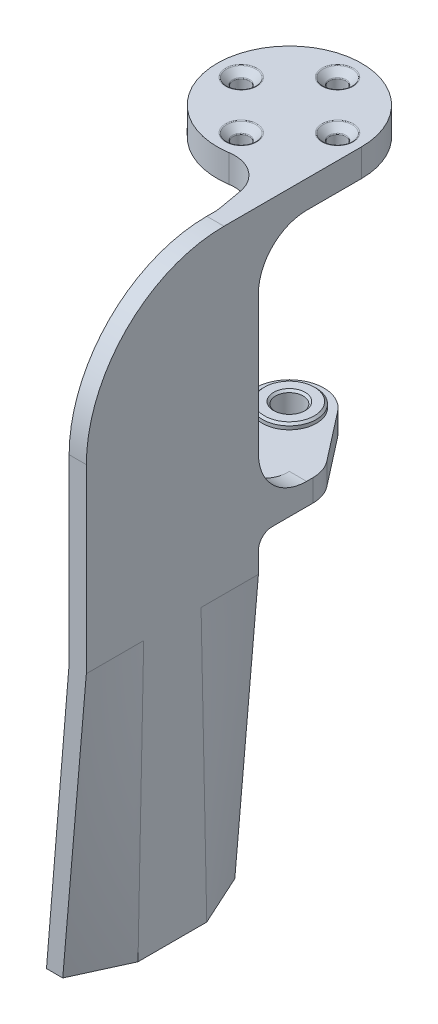
SolidWorks part; units mm, degrees
ref_plane "Front Plane" through (0, 0, 0) normal (0, 0, 1) x (1, 0, 0)
ref_plane "Top Plane" through (0, 0, 0) normal (0, 1, 0) x (1, 0, 0)
ref_plane "Right Plane" through (0, 0, 0) normal (1, 0, 0) x (0, 0, -1)
sketch "Sketch2" plane through (0, 33.6, 0) normal (0, 1, 0) x (1, 0, 0)
  line L0 (10.5, 9.7) -> (10.5, -8.7471)
  line L1 (10.5, -8.7471) -> (10.5, -30.3)
  line L2 (10.5, -30.3) -> (8, -30.3)
  line L3 (8, -30.3) -> (8, -8.7471)
  line L4 (8, -8.7471) -> (6.2367, 1.2529)
  arc A2 (10.5, 9.7) -> (6.2367, 1.2529) centre (0, 9.7) ccw
  circle A3 centre (0, 9.7) radius 9 construction
  dimension "D1" = 1.5
  dimension "D2" = 40
  dimension "D3" = 10
  dimension "D4" = 2.5
  dimension "D5" = 10
extrude "Boss-Extrude1" add sketch "Sketch2" along normal blind 4
hole_wizard "CSK for M2 Countersunk Flat Head Screw1" positions "Sketch3" profile "Sketch4" countersink size "M2" standard "ISO"
sketch "Sketch3" plane through (0, 37.6, 0) normal (0, 1, 0) x (1, 0, 0)
  circle A0 centre (0, 16.7) radius 1 construction
  circle A1 centre (0, 2.7) radius 1 construction
  circle A2 centre (7, 9.7) radius 1 construction
  circle A3 centre (-7, 9.7) radius 1 construction
  point P0 (0, 2.7)
  point P2 (7, 9.7)
  point P4 (0, 16.7)
  point P6 (-7, 9.7)
sketch "Sketch4" plane through (0, 37.6, -2.7) normal (1, 0, 0) x (0, 0, 1)
  line L0 (0, 0) -> (0, 4.721)
  line L1 (0, 4.721) -> (1.2, 4)
  line L2 (1.2, 4) -> (1.2, 1)
  line L3 (1.2, 1) -> (2.2, 0)
  line L5 (2.2, 0) -> (0, 0)
  line L6 (-1.2, 1) -> (-2.2, 0) construction
  line L10 (0, 4.721) -> (-1.2, 4) construction
  line L11 (0, -6.35) -> (0, 107.95) construction
  dimension "Hole Dia." = 2.4
  dimension "Hole Depth" = 4
  dimension "Near C'Sink Dia." = 4.4
  dimension "Near C'Sink Angle" = 90
  dimension "Drill Angle" = 118
sketch "Sketch5" plane through (0, 33.6, 0) normal (0, -1, 0) x (1, 0, 0)
  line L0 (0, -20.2) -> (0, -9.7) construction
  line L1 (-4.82, -20.2) -> (-4.82, -9.7)
  line L2 (4.82, -20.2) -> (4.82, -9.7)
  arc A0 (-4.82, -20.2) -> (4.82, -20.2) centre (0, -20.2) ccw
  arc A1 (4.82, -9.7) -> (-4.82, -9.7) centre (0, -9.7) ccw
  arc A2 (6.2367, -1.2529) -> (10.5, -9.7) centre (0, -9.7) ccw construction
  circle A3 centre (0, -9.7) radius 4.32 construction
  point P4 (0, -14.95)
  dimension "D1" = 0.5
extrude "Cut-Extrude1" cut sketch "Sketch5" against normal blind 1
sketch "Sketch6" plane through (0, 0.5, 0) normal (0, -1, 0) x (1, 0, 0)
  circle A0 centre (0, -9.7) radius 3.92
  circle A1 centre (0, -9.7) radius 4.12 construction
  dimension "D1" = 0.2
extrude "Boss-Extrude2" add sketch "Sketch6" along normal blind 0.8 from offset 0.2 separate body
sketch "Sketch7" plane through (0, -0.5, 0) normal (0, -1, 0) x (1, 0, 0)
  line L0 (-3.9484, -6.6324) -> (8, 8.7471)
  line L1 (8, 8.7471) -> (8, 30.3)
  line L2 (8, 30.3) -> (10.5, 30.3)
  line L3 (10.5, 30.3) -> (10.5, -4.3346)
  line L4 (10.5, -4.3346) -> (3.9484, -12.7676)
  line L5 (10.5, 30.3) -> (10.5, -9.7) construction
  arc A0 (-3.9484, -6.6324) -> (3.9484, -12.7676) centre (0, -9.7) ccw
  dimension "D1" = 5
extrude "Boss-Extrude3" add sketch "Sketch7" along normal blind 3.2
sketch "Sketch10" plane through (0, -3.7, 0) normal (0, -1, 0) x (1, 0, 0)
  circle A0 centre (0, -9.7) radius 2
  dimension "D1" = 4
extrude "Cut-Extrude2" cut sketch "Sketch10" against normal blind 5
sketch "Sketch11" plane through (0, -3.7, 0) normal (0, -1, 0) x (1, 0, 0)
  circle A0 centre (0, -9.7) radius 3.75
  dimension "D1" = 7.5
extrude "Cut-Extrude3" cut sketch "Sketch11" against normal blind 0.4
sketch "Sketch12" plane through (0, 37.6, 0) normal (0, 1, 0) x (1, 0, 0)
  line L0 (8, -8.7471) -> (8, -30.3) construction
  line L1 (10.5, -30.3) -> (8, -30.3)
  line L2 (10.5, -30.3) -> (10.5, -5.3)
  line L3 (10.5, -5.3) -> (8, -5.3)
  line L4 (8, -30.3) -> (8, -5.3)
  dimension "D1" = 25
extrude "Boss-Extrude4" add sketch "Sketch12" against normal offset from surface (46.3 mm away) 5 up to face at (0, -3.7, -13.45) offset beyond the face yes
fillet "Fillet1" radius 7 2 edges at (9.25, -0.5, 5.3) (9.25, 33.6, 5.3)
fillet "Fillet2" radius 20 1 edges at (9.25, 37.6, 30.3)
chamfer "Chamfer1" distance 0.3 angle 45 2 edges at (0, 0.3, -11.7) (0, 0.3, -13.62)
fillet "Fillet3" radius 0.2 2 edges at (0, -3.3, -11.7) (0, -3.3, -13.45)
chamfer "Chamfer2" distance 0.5 angle 45 3 edges at (0, 34.6, -20.2) (4.82, 34.1, -19.0283) (-4.82, 34.1, -19.0283) first distance on face at (0, 34.6, -17.9) first distance on face at (4.82, 34.1, -14.3642) first distance on face at (-4.82, 34.1, -14.3642)
fillet "Fillet4" radius 0.2 12 edges at (0, 37.6, -0.5) (7, 37.6, -7.5) (0, 37.6, -14.5) (-7, 37.6, -7.5) (7, 36.6, -8.5) (7, 33.6, -8.5) (0, 36.6, -1.5) (0, 33.6, -1.5) (-7, 36.6, -8.5) (-7, 33.6, -8.5) (0, 34.6, -17.9) (0, 36.6, -15.5)
fillet "Fillet6" radius 5 3 edges at (8, 35.6, 8.7471) (6.2367, 35.6, -1.2529) (10.5, -2.1, -4.3346)
fillet "Fillet7" radius 2 1 edges at (9.25, -3.7, 5.3)
ref_plane "Plane1" through (0, -48.7, 0) normal (0, 1, 0) x (1, 0, 0)
sketch "Sketch14" plane through (0, -8.7, 0) normal (0, -1, 0) x (1, 0, 0)
  line L0 (22.8976, 21.9667) -> (-9.3679, 21.9667) construction
  line L1 (8, 30.3) -> (10.5, 30.3)
  line L3 (8, 5.3) -> (10.5, 5.3)
  line L5 (22.8976, 13.6333) -> (-9.3679, 13.6333) construction
  line L6 (9.25, 30.3) -> (9.25, 21.9667) construction
  line L7 (9.25, 21.9667) -> (9.25, 13.6333) construction
  line L8 (9.25, 13.6333) -> (9.25, 5.3) construction
  line L9 (8, 30.3) -> (8, 21.9667)
  line L10 (8, 21.9667) -> (8, 13.6333)
  line L11 (8, 13.6333) -> (8, 5.3)
  line L12 (10.5, 5.3) -> (10.5, 13.6333)
  line L13 (10.5, 13.6333) -> (10.5, 21.9667)
  line L14 (10.5, 21.9667) -> (10.5, 30.3)
sketch "Sketch13" plane through (0, -48.7, 0) normal (0, 1, 0) x (1, 0, 0)
  line L0 (4.7083, -5.3) -> (7.0713, -5.3) construction
  line L1 (4.7083, -30.3) -> (7.0713, -30.3) construction
  line L2 (8, -30.3) -> (10.5, -30.3) construction
  line L5 (10.5, -5.3) -> (8, -5.3) construction
  line L6 (10.5, -30.3) -> (10.5, -5.3) construction
  line L13 (10.5, -17.8) -> (-14, -17.8) construction
  line L14 (10.5, -12.8054) -> (10.5, -22.7946)
  line L15 (10.5, -22.7946) -> (7.0713, -30.3)
  line L16 (7.0713, -30.3) -> (4.7083, -30.3)
  line L17 (4.7083, -30.3) -> (8.5, -22)
  line L18 (8.5, -22) -> (8.5, -13.6)
  line L19 (4.7083, -5.3) -> (8.5, -13.6)
  line L20 (7.0713, -5.3) -> (4.7083, -5.3)
  line L21 (10.5, -12.8054) -> (7.0713, -5.3)
  arc A0 (4.7083, -30.3) -> (4.7083, -5.3) centre (-14, -17.8) ccw construction
  arc A1 (7.0713, -30.3) -> (7.0713, -5.3) centre (-14, -17.8) ccw construction
  point P17 (8.5, -17.8)
  dimension "D1" = 2
  dimension "D2" = 45
  dimension "D3" = 4.2
loft "Loft1" add profiles "Sketch14", "Sketch13" connector at (8, -8.7, 30.3) connector at (4.7083, -48.7, 30.3)
